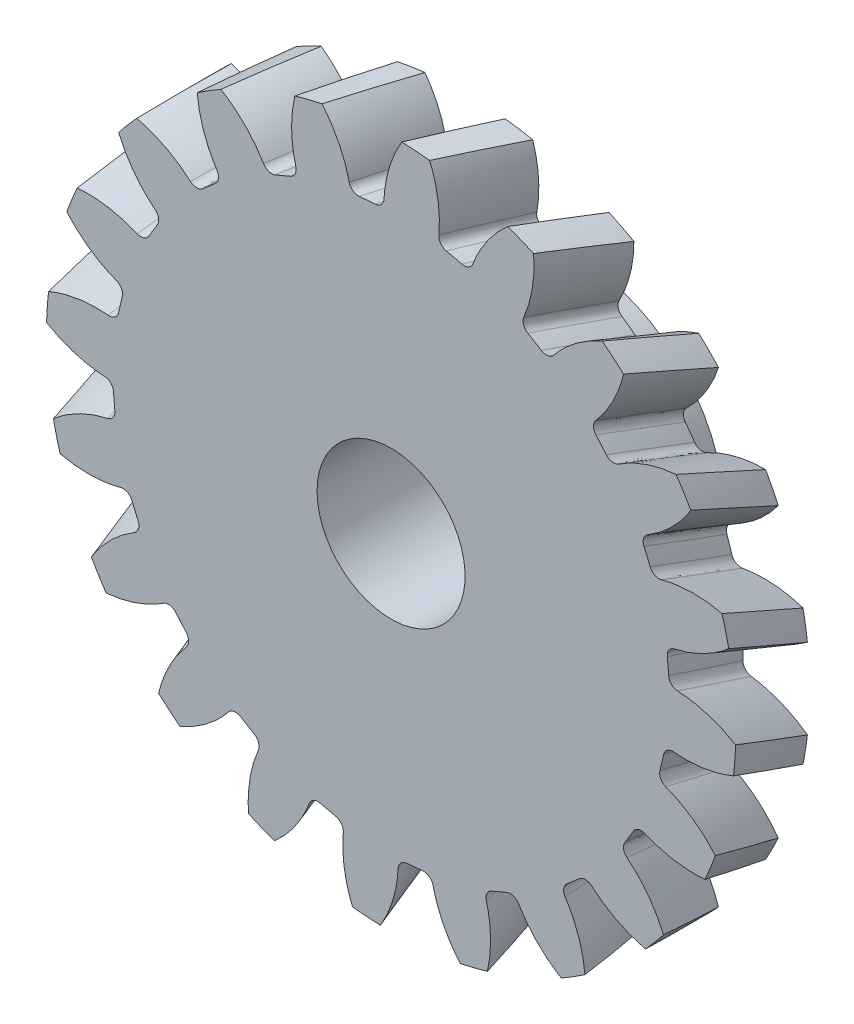
SolidWorks part; units mm, degrees
ref_plane "Front" through (0, 0, 0) normal (0, 0, 1) x (1, 0, 0)
ref_plane "Top" through (0, 0, 0) normal (0, 1, 0) x (1, 0, 0)
ref_plane "Right" through (0, 0, 0) normal (1, 0, 0) x (0, 0, -1)
sketch "gearBodySketch" plane through (0, 0, 0) normal (0, 0, 1) x (1, 0, 0)
  circle A0 centre (0, 0) radius 29.5707
  dimension "od" = 59.1414
extrude "gearBody" add sketch "gearBodySketch" along normal blind 6.35
sketch "toothSketchLH" plane through (0, 0, 0) normal (0, 0, 1) x (1, 0, 0)
  line L0 (2.1208, 26.9474) -> (12.082, 23.0919) construction
  line L1 (0, 0) -> (0, 27.0307) construction
  line L2 (0, 0) -> (2.1208, 26.9474) construction
  line L3 (0, 279.4) -> (0, 0) construction
  arc A0 (0.6807, 23.846) -> (-0.6807, 23.846) centre (0, 0) ccw
  circle A1 centre (0, 0) radius 26.0617 construction
  circle A2 centre (0, 0) radius 27.0307 construction
  circle A3 centre (0, 0) radius 29.5707 construction
  arc A4 (3.4576, 29.3934) -> (-3.4576, 29.3934) centre (0, 0) ccw
  arc A5 (3.4576, 29.3934) -> (1.4993, 24.5398) centre (12.082, 23.0919) ccw
  arc A6 (0.6807, 23.846) -> (1.4993, 24.5398) centre (0.7037, 24.6487) ccw
  arc A7 (-0.6807, 23.846) -> (-1.4993, 24.5398) centre (-0.7037, 24.6487) cw
  arc A8 (-3.4576, 29.3934) -> (-1.4993, 24.5398) centre (-12.082, 23.0919) cw
  dimension "D1" = 279.4
  dimension "minorDiameter" = 47.7114
  dimension "baseDia" = 52.1234
  dimension "pd" = 54.0614
  dimension "od" = 59.1414
  dimension "overOD" = 59.1922
  dimension "flankRadius2" = 10.6813
  dimension "rFillet" = 0.8031
  dimension "toothAng" = 4.5
  dimension "flankRadius" = 10.6813
sketch "helixLH" plane through (0, 0, 0) normal (0, 0, -1) x (-1, 0, 0)
  circle A0 centre (0, 0) radius 27.0307
  dimension "pd" = 54.0614
curve "Helix/Spiral1" pitch 466.6282 height 6.35 turns 0.0136 parameters "pitch"=6.35, "pitch1"=466.6282
sketch "Sketch3" plane through (0, 0, 0) normal (0, 0, -1) x (-1, 0, 0)
  line L0 (0, 0) -> (0, 27.0307) construction
  circle A0 centre (0, 0) radius 27.0307 construction
sketch "masterToothSketch" plane through (0, 0, 0) normal (0, 0, -1) x (-1, 0, 0)
  line L0 (2.1208, 26.9474) -> (12.082, 23.0919) construction
  line L1 (0, 0) -> (0, 27.0307) construction
  line L2 (0, 0) -> (2.1208, 26.9474) construction
  line L3 (0, 279.4) -> (0, 0) construction
  arc A0 (0.6807, 23.846) -> (-0.5607, 23.8491) centre (0, 0) ccw
  circle A1 centre (0, 0) radius 26.0617 construction
  circle A2 centre (0, 0) radius 27.0307 construction
  circle A3 centre (0, 0) radius 29.5707 construction
  arc A4 (3.4576, 29.3934) -> (-2.1627, 29.517) centre (0, 0) ccw
  arc A5 (3.4576, 29.3934) -> (1.4993, 24.5398) centre (12.082, 23.0919) ccw
  arc A6 (0.6807, 23.846) -> (1.4993, 24.5398) centre (0.7037, 24.6487) ccw
  arc A7 (-0.6807, 23.846) -> (-1.4993, 24.5398) centre (-0.7037, 24.6487) cw
  arc A8 (-3.4576, 29.3934) -> (-1.4993, 24.5398) centre (-12.082, 23.0919) cw
  dimension "masterMinorDiam" = 47.7114
  dimension "masterBaseDiam" = 52.1234
  dimension "masterPD" = 54.0614
  dimension "masterOD" = 59.1414
  dimension "masterOverOD" = 59.1922
  dimension "masterFlankRadius2" = 10.6813
  dimension "masterRfillet" = 0.8031
  dimension "masterToothAngle" = 4.5
  dimension "masterFlankRadius" = 10.6813
  dimension "D10" = 279.4
sketch "toothSketchRH" plane through (0, 0, 0) normal (0, 0, 1) x (1, 0, 0)
  line L0 (2.1208, 26.9474) -> (12.082, 23.0919) construction
  line L1 (0, 0) -> (0, 27.0307) construction
  line L2 (0, 0) -> (2.1208, 26.9474) construction
  line L3 (0, 279.4) -> (0, 0) construction
  arc A0 (0.6807, 23.846) -> (-0.6807, 23.846) centre (0, 0) ccw
  circle A1 centre (0, 0) radius 26.0617 construction
  circle A2 centre (0, 0) radius 27.0307 construction
  circle A3 centre (0, 0) radius 29.5707 construction
  arc A4 (3.4576, 29.3934) -> (-3.4576, 29.3934) centre (0, 0) ccw
  arc A5 (3.4576, 29.3934) -> (1.4993, 24.5398) centre (12.082, 23.0919) ccw
  arc A6 (0.6807, 23.846) -> (1.4993, 24.5398) centre (0.7037, 24.6487) ccw
  arc A7 (-0.6807, 23.846) -> (-1.4993, 24.5398) centre (-0.7037, 24.6487) cw
  arc A8 (-3.4576, 29.3934) -> (-1.4993, 24.5398) centre (-12.082, 23.0919) cw
  dimension "minorDiameter" = 47.7114
  dimension "baseDia" = 52.1234
  dimension "pd" = 54.0614
  dimension "od" = 59.1414
  dimension "overOD" = 59.1922
  dimension "flankRadius2" = 10.6813
  dimension "rFillet" = 0.8031
  dimension "toothAng" = 4.5
  dimension "flankRadius" = 10.6813
  dimension "D10" = 279.4
sketch "helixRH" plane through (0, 0, 0) normal (0, 0, 1) x (1, 0, 0)
  circle A0 centre (0, 0) radius 27.0307
  dimension "pd" = 54.0614
curve "Helix/Spiral2"
sweep "toothCutRH" cut profiles "toothSketchRH" path "Helix/Spiral2"
pattern_circular "CirPattern2" count 20 over 360 about axis through (0, 0, 6.35) along (0, 0, -1) of "toothCutRH"
sketch "hd1Sketch" plane through (0, 0, 0) normal (0, 0, -1) x (-1, 0, 0)
  circle A0 centre (0, 0) radius 12.7
  dimension "hd" = 25.4
extrude "hub1" add sketch "hd1Sketch" along normal blind 9.525
sketch "hd2Sketch" plane through (0, 0, 6.35) normal (0, 0, 1) x (1, 0, 0)
  circle A0 centre (0, 0) radius 12.7
  dimension "hd" = 25.4
ref_plane "CB1plane" through (0, 0, -9.525) normal (0, 0, -1) x (-1, 0, 0)
sketch "CB1diameter" plane through (0, 0, -9.525) normal (0, 0, -1) x (-1, 0, 0)
  circle A0 centre (0, 0) radius 12.7
  dimension "CB1diameter" = 25.4
ref_plane "CB2plane" through (0, 0, 6.35) normal (0, 0, 1) x (1, 0, 0)
sketch "CB2diameter" plane through (0, 0, 6.35) normal (0, 0, 1) x (1, 0, 0)
  circle A0 centre (0, 0) radius 12.7
  dimension "CB2diameter" = 25.4
sketch "boreSketch" plane through (0, 0, 0) normal (0, 0, -1) x (-1, 0, 0)
  circle A0 centre (0, 0) radius 6.35
  dimension "bore" = 12.7
extrude "bore" cut sketch "boreSketch" against normal mid plane 25400
sketch "kwy1sketch" plane through (0, 0, 0) normal (0, 0, -1) x (-1, 0, 0)
  line L0 (0, 0) -> (0.06, 23.8556) construction
  line L1 (0, 0) -> (-0.0037, 0.0357) construction
  line L2 (-15.873, 30.2886) -> (9.3944, 32.88)
  line L3 (9.3944, 32.88) -> (12.6337, 1.2957)
  line L4 (-15.873, 30.2886) -> (-12.6337, -1.2957)
  line L5 (12.6337, 1.2957) -> (0, 0)
  line L6 (-12.6337, -1.2957) -> (0, 0)
  arc A3 (0.6807, 23.846) -> (-0.5607, 23.8491) centre (0, 0) ccw construction
  dimension "kwy1width" = 25.4
  dimension "kwy1depth" = 31.75
  dimension "kwy1depth2" = 31.75
  dimension "kwy1angle" = 6
sketch "kwy2sketch" plane through (0, 0, 0) normal (0, 0, -1) x (-1, 0, 0)
  line L0 (0, 0) -> (0.06, 23.8556) construction
  line L1 (0, 0) -> (-24.624, 20.043) construction
  line L2 (-32.6412, 10.1933) -> (-16.6068, 29.8926)
  line L3 (-16.6068, 29.8926) -> (8.0172, 9.8496)
  line L4 (-32.6412, 10.1933) -> (-8.0172, -9.8496)
  line L5 (8.0172, 9.8496) -> (0, 0)
  line L6 (-8.0172, -9.8496) -> (0, 0)
  arc A2 (0.6807, 23.846) -> (-0.5607, 23.8491) centre (0, 0) ccw construction
  dimension "kwy2width" = 25.4
  dimension "kwy2depth" = 31.75
  dimension "kwy2depth2" = 31.75
  dimension "kwy2angle" = 51
sketch "kwy3sketch" plane through (0, 0, 0) normal (0, 0, -1) x (-1, 0, 0)
  line L0 (0, 0) -> (0.06, 23.8556) construction
  line L1 (0, 0) -> (-31.5843, -3.2393) construction
  line L2 (-30.2886, -15.873) -> (-32.88, 9.3944)
  line L3 (-32.88, 9.3944) -> (-1.2957, 12.6337)
  line L4 (-30.2886, -15.873) -> (1.2957, -12.6337)
  line L5 (-1.2957, 12.6337) -> (0, 0)
  line L6 (1.2957, -12.6337) -> (0, 0)
  arc A1 (0.6807, 23.846) -> (-0.5607, 23.8491) centre (0, 0) ccw construction
  dimension "kwy3width" = 25.4
  dimension "kwy3depth" = 31.75
  dimension "kwy3depth2" = 31.75
  dimension "kwy3angle" = 96
sketch "kwy4sketch" plane through (0, 0, 0) normal (0, 0, -1) x (-1, 0, 0)
  line L0 (0, 0) -> (0.06, 23.8556) construction
  line L1 (0, 0) -> (-20.043, -24.624) construction
  line L2 (-10.1933, -32.6412) -> (-29.8926, -16.6068)
  line L3 (-29.8926, -16.6068) -> (-9.8496, 8.0172)
  line L4 (-10.1933, -32.6412) -> (9.8496, -8.0172)
  line L5 (-9.8496, 8.0172) -> (0, 0)
  line L6 (9.8496, -8.0172) -> (0, 0)
  arc A1 (0.6807, 23.846) -> (-0.5607, 23.8491) centre (0, 0) ccw construction
  dimension "kwy4width" = 25.4
  dimension "kwy4depth" = 31.75
  dimension "kwy4depth2" = 31.75
  dimension "kwy4angle" = 141
sketch "kwy5sketch" plane through (0, 0, 0) normal (0, 0, -1) x (-1, 0, 0)
  line L0 (0, 0) -> (0.06, 23.8556) construction
  line L1 (0, 0) -> (3.2393, -31.5843) construction
  line L2 (15.873, -30.2886) -> (-9.3944, -32.88)
  line L3 (-9.3944, -32.88) -> (-12.6337, -1.2957)
  line L4 (15.873, -30.2886) -> (12.6337, 1.2957)
  line L5 (-12.6337, -1.2957) -> (0, 0)
  line L6 (12.6337, 1.2957) -> (0, 0)
  arc A1 (0.6807, 23.846) -> (-0.5607, 23.8491) centre (0, 0) ccw construction
  dimension "kwy5width" = 25.4
  dimension "kwy5depth" = 31.75
  dimension "kwy5depth2" = 31.75
  dimension "kwy5angle" = 186
sketch "kwy6sketch" plane through (0, 0, 0) normal (0, 0, -1) x (-1, 0, 0)
  line L0 (0, 0) -> (0.06, 23.8556) construction
  line L1 (0, 0) -> (24.624, -20.043) construction
  line L2 (32.6412, -10.1933) -> (16.6068, -29.8926)
  line L3 (16.6068, -29.8926) -> (-8.0172, -9.8496)
  line L4 (32.6412, -10.1933) -> (8.0172, 9.8496)
  line L5 (-8.0172, -9.8496) -> (0, 0)
  line L6 (8.0172, 9.8496) -> (0, 0)
  arc A1 (0.6807, 23.846) -> (-0.5607, 23.8491) centre (0, 0) ccw construction
  dimension "kwy6width" = 25.4
  dimension "kwy6depth" = 31.75
  dimension "kwy6depth2" = 31.75
  dimension "kwy6angle" = 231
sketch "kwy7sketch" plane through (0, 0, 0) normal (0, 0, -1) x (-1, 0, 0)
  line L0 (0, 0) -> (0.06, 23.8556) construction
  line L1 (0, 0) -> (31.5843, 3.2393) construction
  line L2 (30.2886, 15.873) -> (32.88, -9.3944)
  line L3 (32.88, -9.3944) -> (1.2957, -12.6337)
  line L4 (30.2886, 15.873) -> (-1.2957, 12.6337)
  line L5 (1.2957, -12.6337) -> (0, 0)
  line L6 (-1.2957, 12.6337) -> (0, 0)
  arc A1 (0.6807, 23.846) -> (-0.5607, 23.8491) centre (0, 0) ccw construction
  dimension "kwy7width" = 25.4
  dimension "kwy7depth" = 31.75
  dimension "kwy7depth2" = 31.75
  dimension "kwy7angle" = 276
sketch "kwy8sketch" plane through (0, 0, 0) normal (0, 0, -1) x (-1, 0, 0)
  line L0 (0, 0) -> (0.06, 23.8556) construction
  line L1 (0, 0) -> (20.043, 24.624) construction
  line L2 (10.1933, 32.6412) -> (29.8926, 16.6068)
  line L3 (29.8926, 16.6068) -> (9.8496, -8.0172)
  line L4 (10.1933, 32.6412) -> (-9.8496, 8.0172)
  line L5 (9.8496, -8.0172) -> (0, 0)
  line L6 (-9.8496, 8.0172) -> (0, 0)
  arc A1 (0.6807, 23.846) -> (-0.5607, 23.8491) centre (0, 0) ccw construction
  dimension "kwy8width" = 25.4
  dimension "kwy8depth" = 31.75
  dimension "kwy8depth2" = 31.75
  dimension "kwy8angle" = 321
sketch3d "ss2posLines"
  line L0 (0, 29.5707, 0) -> (0, 29.5707, 12.7) construction
  line L1 (0, 29.5707, 12.7) -> (0, 0, 0) construction
  line L2 (0, 29.5707, 0) -> (0, 0, 0) construction
  circle A0 centre (0, 0, 0) radius 29.5707 construction
  point P5 (0, 0, 29.5707)
  dimension "faceWidth" = 12.7
